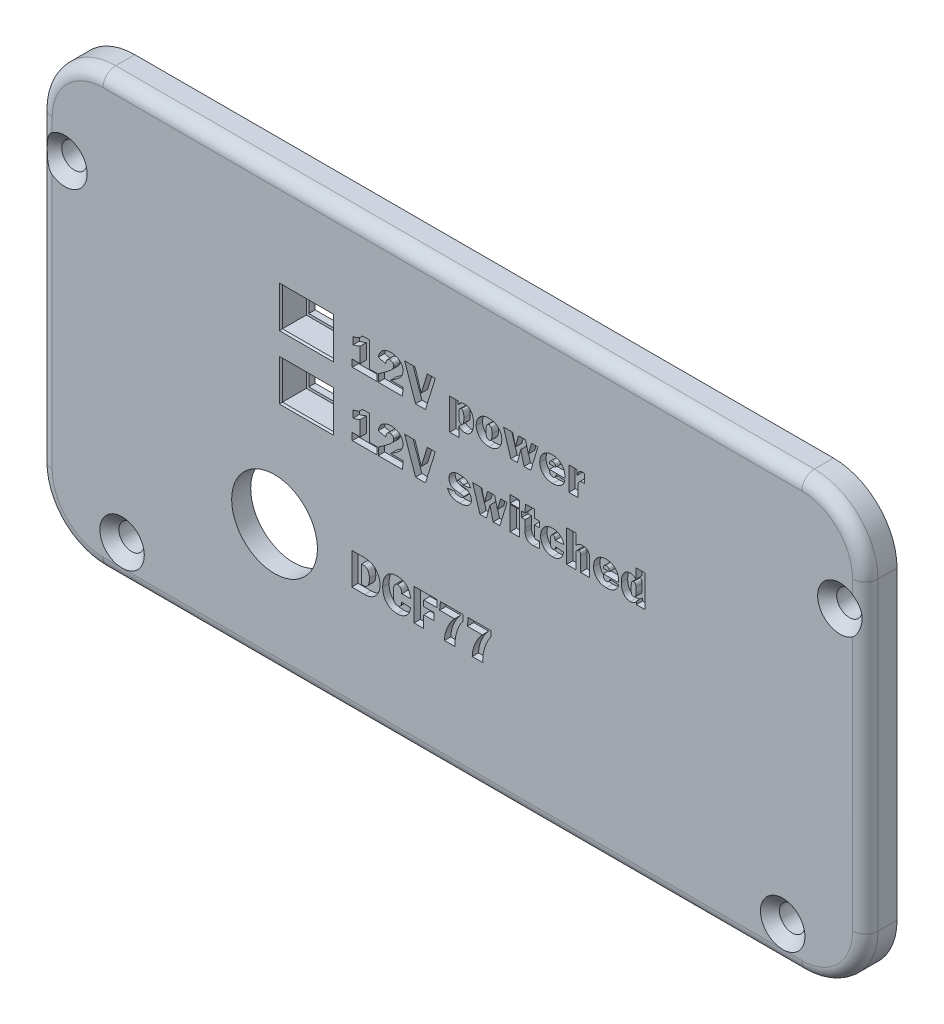
SolidWorks part; units mm, degrees
ref_plane "Front Plane" through (0, 0, 0) normal (0, 0, 1) x (1, 0, 0)
ref_plane "Top Plane" through (0, 0, 0) normal (0, 1, 0) x (1, 0, 0)
ref_plane "Right Plane" through (0, 0, 0) normal (1, 0, 0) x (0, 0, -1)
sketch "Sketch1" plane through (0, 0, 0) normal (0, 0, 1) x (1, 0, 0)
  line L0 (-55, 21) -> (55, -27) construction
  line L1 (-57, -26) -> (57, -26) construction
  line L2 (-57, -26) -> (-57, 26) construction
  line L3 (-57, 26) -> (57, 26) construction
  line L4 (57, -26) -> (57, 26) construction
  line L5 (-57, -26) -> (57, 26) construction
  line L6 (-57, 26) -> (57, -26) construction
  line L7 (-55, -37) -> (55, -37)
  line L8 (-65, -27) -> (-65, 21)
  line L9 (-55, 31) -> (55, 31)
  line L10 (65, -27) -> (65, 21)
  line L11 (55, 21) -> (-55, -27) construction
  line L12 (-62, -27) -> (-62, 21) construction
  line L13 (-55, 28) -> (55, 28) construction
  line L14 (62, -27) -> (62, 21) construction
  line L15 (-55, -34) -> (55, -34) construction
  line L16 (0, 0) -> (0, -3) construction
  line L17 (0, 26) -> (0, 31) construction
  line L18 (-62, -3) -> (-57, -3) construction
  arc A0 (55, 31) -> (65, 21) centre (55, 21) cw
  arc A1 (55, -37) -> (65, -27) centre (55, -27) ccw
  arc A2 (-55, -37) -> (-65, -27) centre (-55, -27) cw
  arc A3 (-65, 21) -> (-55, 31) centre (-55, 21) cw
  arc A4 (-55, -34) -> (-62, -27) centre (-55, -27) cw construction
  arc A5 (-62, 21) -> (-55, 28) centre (-55, 21) cw construction
  arc A6 (55, 28) -> (62, 21) centre (55, 21) cw construction
  arc A7 (55, -34) -> (62, -27) centre (55, -27) ccw construction
  point P0 (0, 0)
  point P6 (0, 0)
  dimension "D3" = 10
  dimension "D1" = 130
  dimension "D2" = 52
  dimension "D4" = 5
  dimension "D5" = 3
  dimension "D6" = 3
extrude "Boss-Extrude1" add sketch "Sketch1" along normal blind 5
sketch "Sketch2" plane through (0, 0, 0) normal (0, 0, -1) x (-1, 0, 0)
  line L1 (55, -37) -> (-55, -37) construction
  line L2 (65, 21) -> (65, -27) construction
  line L3 (-65, -26) -> (65, -26) construction
  line L4 (-65, -27) -> (-65, 21) construction
  circle A0 centre (28, -17) radius 6.75
  circle A1 centre (28, -17) radius 9 construction
  dimension "D1" = 13.5
  dimension "D3" = 18
  dimension "D2" = 37
  dimension "D4" = 11
extrude "Cut-Extrude1" cut sketch "Sketch2" against normal through all
sketch "Sketch3" plane through (0, 0, 0) normal (0, 0, -1) x (-1, 0, 0)
  line L0 (-46.5, 19) -> (13.5, 19) construction
  line L1 (-65, -27) -> (-65, 21) construction
  circle A0 centre (-46.5, 19) radius 1.8
  circle A1 centre (13.5, 19) radius 1.8
  circle A2 centre (-50.43, -14.1) radius 1.8
  circle A3 centre (2.5, -15) radius 1.8
  dimension "D2" = 3.6
  dimension "D1" = 60
  dimension "D3" = 19
  dimension "D4" = 18.5
  dimension "D5" = 33.1
  dimension "D6" = 3.93
  dimension "D7" = 34
  dimension "D8" = 11
extrude "Cut-Extrude2" cut sketch "Sketch3" against normal offset from surface (3 mm away) 2 up to face at (-34.75, -17, 5)
sketch "Sketch6" plane through (0, 0, 0) normal (0, 0, -1) x (-1, 0, 0)
  circle A0 centre (28, -17) radius 11
  dimension "D1" = 22
extrude "Cut-Extrude4" cut sketch "Sketch6" against normal offset from surface (2 mm away) 3 up to face at (-34.75, -17, 5)
sketch "Sketch7" plane through (0, 0, 5) normal (0, 0, 1) x (1, 0, 0)
  line L0 (-23, 13) -> (-23, 3) construction
  line L1 (-27, 0) -> (-19, 0)
  line L2 (-27, 0) -> (-27, 6)
  line L3 (-27, 6) -> (-19, 6)
  line L4 (-19, 0) -> (-19, 6)
  line L5 (-27, 0) -> (-19, 6) construction
  line L6 (-27, 6) -> (-19, 0) construction
  line L7 (-27, 10) -> (-19, 10)
  line L8 (-27, 10) -> (-27, 16)
  line L9 (-27, 16) -> (-19, 16)
  line L10 (-19, 10) -> (-19, 16)
  line L11 (-27, 10) -> (-19, 16) construction
  line L12 (-27, 16) -> (-19, 10) construction
  line L13 (-23, 3) -> (-23, -17) construction
  circle A1 centre (-28, -17) radius 6.75 construction
  circle A2 centre (-28, -17) radius 6.75 construction
  point P0 (-23, 3)
  point P5 (-23, 13)
  point P18 (0, 0)
  dimension "D5" = 5
  dimension "D1" = 8
  dimension "D2" = 6
  dimension "D3" = 20
  dimension "D4" = 10
extrude "Cut-Extrude5" cut sketch "Sketch7" against normal through all
sketch "Sketch8" plane through (0, 0, 5) normal (0, 0, 1) x (1, 0, 0)
  line L0 (-16.25, 10.5) -> (65, 10.5) construction
  line L2 (-16.25, 0.5) -> (65, 0.5) construction
  line L4 (-16.25, -19.5) -> (65, -19.5) construction
  line L5 (-19, 10) -> (-19, 16) construction
  line L7 (-19, 13) -> (-19, 10.5) construction
  line L8 (-19, 3) -> (-19, 0.5) construction
  line L9 (65, -27) -> (65, 21) construction
  line L10 (-21.25, -17) -> (-21.25, -19.5) construction
  line L11 (-21.25, -17) -> (-28, -17) construction
  line L12 (-19, 10.5) -> (-16.25, 10.5) construction
  line L13 (-19, 0) -> (-19, 6) construction
  line L14 (-19, 0.5) -> (-16.25, 0.5) construction
  line L15 (-16.25, -19.5) -> (-21.25, -19.5) construction
  line L16 (-16.25, 10.5) -> (-16.25, 0.5) construction
  line L17 (-16.25, 0.5) -> (-16.25, -19.5) construction
  circle A0 centre (-28, -17) radius 6.75 construction
  text T0 "12V power" font "Franklin Gothic Heavy" height 5
  text T1 "12V switched" font "Franklin Gothic Heavy" height 5
  text T2 "DCF77" font "Franklin Gothic Heavy" height 5
  point P2 (-19.25, 10.5)
  dimension "D1" = 2.5
  dimension "D2" = 5
extrude "Cut-Extrude6" cut sketch "Sketch8" against normal blind 1
sketch "Sketch9" plane through (0, 0, 0) normal (0, 0, -1) x (-1, 0, 0)
  line L0 (27, 6) -> (27, 0) construction
  line L1 (27, 0) -> (19, 0) construction
  line L2 (19, 0) -> (19, 6) construction
  line L3 (19, 6) -> (27, 6) construction
  line L4 (19, 16) -> (27, 16) construction
  line L5 (27, 16) -> (27, 10) construction
  line L6 (27, 10) -> (19, 10) construction
  line L7 (19, 10) -> (19, 16) construction
  line L8 (27, 6) -> (27, 0)
  line L9 (27, 0) -> (19, 0)
  line L10 (19, 0) -> (19, 6)
  line L11 (19, 6) -> (27, 6)
  line L12 (19, 16) -> (27, 16)
  line L13 (27, 16) -> (27, 10)
  line L14 (27, 10) -> (19, 10)
  line L15 (19, 10) -> (19, 16)
  line L16 (19.4, 15.6) -> (26.6, 15.6)
  line L17 (26.6, 15.6) -> (26.6, 10.4)
  line L18 (26.6, 10.4) -> (19.4, 10.4)
  line L19 (19.4, 10.4) -> (19.4, 15.6)
  line L20 (26.6, 5.6) -> (26.6, 0.4)
  line L21 (26.6, 0.4) -> (19.4, 0.4)
  line L22 (19.4, 0.4) -> (19.4, 5.6)
  line L23 (19.4, 5.6) -> (26.6, 5.6)
  line L24 (23, 15.6) -> (23, 16) construction
  line L25 (23, 5.6) -> (23, 6) construction
  dimension "D1" = 0.4
extrude "Boss-Extrude2" add sketch "Sketch9" against normal blind 1
sketch "Sketch10" plane through (0, 0, 0) normal (0, 0, -1) x (-1, 0, 0)
  circle A8 centre (-46.5, 19) radius 4
  circle A9 centre (13.5, 19) radius 4
  circle A10 centre (2.5, -15) radius 4
  circle A11 centre (-50.43, -14.1) radius 4
  dimension "D1" = 8
extrude "Boss-Extrude3" add sketch "Sketch10" along normal blind 5
sketch "Sketch11" plane through (0, 0, 0) normal (0, 0, -1) x (-1, 0, 0)
  line L0 (55, -37) -> (-55, -37) construction
  line L1 (-45.55, 4.71) -> (-35.55, 4.71)
  line L2 (-45.55, 4.71) -> (-45.55, -5.29)
  line L3 (-45.55, -5.29) -> (-35.55, -5.29)
  line L4 (-35.55, 4.71) -> (-35.55, -5.29)
  line L5 (-45.55, 4.71) -> (-35.55, -5.29) construction
  line L6 (-45.55, -5.29) -> (-35.55, 4.71) construction
  line L7 (-65, -27) -> (-65, 21) construction
  point P0 (-40.55, -0.29)
  point P21 (0, 0)
  dimension "D1" = 36.71
  dimension "D2" = 10
  dimension "D3" = 24.45
extrude "Cut-Extrude7" cut sketch "Sketch11" against normal blind 3
fillet "Fillet1" radius 1 8 edges at (40.55, -5.29, 3) (45.55, -0.29, 3) (40.55, 4.71, 3) (35.55, -0.29, 3) (45.55, -5.29, 1.5) (35.55, -5.29, 1.5) (35.55, 4.71, 1.5) (45.55, 4.71, 1.5)
sketch "Sketch12" plane through (0, 0, 5) normal (0, 0, 1) x (1, 0, 0)
  line L0 (-61, -31.5) -> (-52, -31.5) construction
  line L5 (0, 16) -> (0, -31.5) construction
  line L6 (-61, 16) -> (61, 16) construction
  line L7 (-61, 16) -> (-61, -31.5) construction
  line L8 (-61, -31.5) -> (61, -31.5) construction
  line L9 (61, 16) -> (61, -31.5) construction
  line L10 (55, 31) -> (-55, 31) construction
  line L11 (-55, -37) -> (55, -37) construction
  line L12 (-65, 21) -> (-65, -27) construction
  line L13 (52, -31.5) -> (61, -31.5) construction
  circle A0 centre (-61, 16) radius 2
  circle A1 centre (61, 16) radius 2
  circle A2 centre (52, -31.5) radius 2
  circle A3 centre (-52, -31.5) radius 2
  dimension "D4" = 4
  dimension "D1" = 15
  dimension "D2" = 5.5
  dimension "D3" = 4
  dimension "D5" = 9
extrude "Cut-Extrude8" cut sketch "Sketch12" against normal through all
sketch "Sketch13" plane through (0, 0, -5) normal (0, 0, -1) x (-1, 0, 0)
  circle A0 centre (-46.5, 19) radius 2.1
  circle A1 centre (13.5, 19) radius 2.1
  circle A2 centre (2.5, -15) radius 2.1
  circle A3 centre (-50.43, -14.1) radius 2.1
  dimension "D1" = 4.2
extrude "Cut-Extrude9" cut sketch "Sketch13" against normal blind 3
sketch "Sketch14" plane through (0, 0, -5) normal (0, 0, -1) x (-1, 0, 0)
  circle A0 centre (-46.5, 19) radius 1.8
  circle A1 centre (13.5, 19) radius 1.8
  circle A2 centre (2.5, -15) radius 1.8
  circle A3 centre (-50.43, -14.1) radius 1.8
  dimension "D1" = 3.6
extrude "Cut-Extrude10" cut sketch "Sketch14" against normal offset from surface (7 mm away) 3 up to face at (-59, 16, 5)
fillet "Fillet3" radius 2 4 edges at (46.43, -14.1, 0) (-6.5, -15, 0) (-17.5, 19, 0) (42.5, 19, 0)
chamfer "Chamfer1" distance 1.5 angle 45 4 edges at (-59, 16, 5) (63, 16, 5) (54, -31.5, 5) (-50, -31.5, 5)
fillet "Fillet2" radius 2 8 edges at (62.0711, 28.0711, 5) (65, -3, 5) (62.0711, -34.0711, 5) (0, -37, 5) (-62.0711, -34.0711, 5) (-65, -3, 5) (-62.0711, 28.0711, 5) (0, 31, 5)
chamfer "Chamfer2" distance 0.25 angle 45 8 edges at (-19, 3, 5) (-23, 0, 5) (-27, 3, 5) (-23, 6, 5) (-27, 13, 5) (-23, 10, 5) (-19, 13, 5) (-23, 16, 5)
